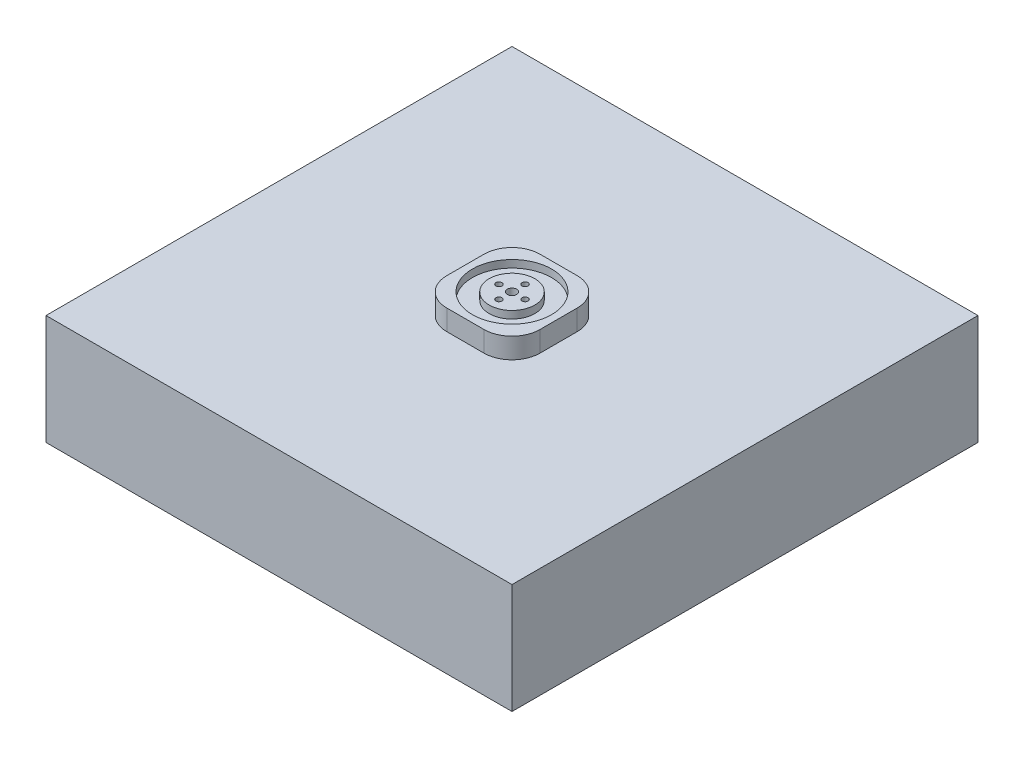
SolidWorks part; units mm, degrees
ref_plane "Front Plane" through (0, 0, 0) normal (0, 0, 1) x (1, 0, 0)
ref_plane "Top Plane" through (0, 0, 0) normal (0, 1, 0) x (1, 0, 0)
ref_plane "Right Plane" through (0, 0, 0) normal (1, 0, 0) x (0, 0, -1)
sketch "Sketch1" plane through (0, 0, 0) normal (0, 0, 1) x (1, 0, 0)
  line L0 (-22.5, 0) -> (22.5, 0)
  line L1 (-18, 9) -> (18, 9)
  line L2 (-18, 9) -> (-22.5, 0)
  line L3 (18, 9) -> (22.5, 0)
  point P4 (0, 0)
  point P8 (0, 9)
  dimension "D1" = 45
  dimension "D2" = 36
  dimension "D3" = 9
extrude "Boss-Extrude1" add sketch "Sketch1" along normal blind 44
sketch "Sketch3" plane through (0, 9, 0) normal (0, 1, 0) x (1, 0, 0)
  line L0 (18, -44) -> (18, 0) construction
  line L1 (-25, -47) -> (25, -47)
  line L2 (-25, -47) -> (-25, 3)
  line L3 (-25, 3) -> (25, 3)
  line L4 (25, -47) -> (25, 3)
  line L5 (-25, -47) -> (25, 3) construction
  line L6 (-25, 3) -> (25, -47) construction
  point P0 (0, -22)
  point P10 (18, -22)
  dimension "D1" = 50
  dimension "D2" = 50
extrude "Boss-Extrude2" add sketch "Sketch3" along normal blind 11
sketch "Sketch4" plane through (0, 20, 0) normal (0, 1, 0) x (1, 0, 0)
  line L0 (25, -47) -> (25, 3) construction
  circle A0 centre (0, -22) radius 12.25
  circle A1 centre (0, -22) radius 21.25
  point P6 (25, -22)
  dimension "D1" = 24.5
  dimension "D2" = 42.5
extrude "Cut-Extrude1" cut sketch "Sketch4" against normal blind 4
sketch "Sketch5" plane through (0, 20, 0) normal (0, 1, 0) x (1, 0, 0)
  circle A0 centre (0, -22) radius 12.25
  circle A1 centre (0, -22) radius 12.25 construction
  circle A2 centre (0, -22) radius 10.05
  circle A3 centre (0, -15) radius 1.6
  circle A4 centre (7, -22) radius 1.6
  circle A5 centre (0, -22) radius 10.05
  circle A6 centre (0, -29) radius 1.6
  circle A7 centre (0, -22) radius 10.05
  circle A8 centre (-7, -22) radius 1.6
  circle A9 centre (0, -22) radius 10.05
  circle A10 centre (0, -22) radius 2.5
  point P19 (0, -22)
  dimension "D1" = 20.1
  dimension "D2" = 3.2
  dimension "D5" = 5
  dimension "D3" = 7
  dimension "D4" = 4
extrude "Cut-Extrude3" cut sketch "Sketch5<3>" along direction (0, 1, 0) on the side against the normal up to surface (20 mm away) contours A3 | A8 | A4 | A6 region at (0, 20, 15) region at (7, 20, 22) region at (0, 20, 29) region at (-7, 20, 22) up to face at (0, 0, 22)
sketch "Sketch5<3>" plane through (0, 20, 0) normal (0, 1, 0) x (1, 0, 0) same geometry as "Sketch5"
extrude "Cut-Extrude4" cut sketch "Sketch5" against normal blind 5 contours A10 region at (0, 20, 22)
sketch "Sketch8" plane through (0, 0, 0) normal (0, -1, 0) x (-1, 0, 0)
  circle A0 centre (0, -29) radius 3
  circle A1 centre (-7, -22) radius 3
  circle A2 centre (0, -15) radius 3
  circle A3 centre (7, -22) radius 3
  dimension "D1" = 6
fillet "Fillet2" radius 15 4 edges at (-25, 14.5, 47) (-25, 14.5, -3) (25, 14.5, -3) (25, 14.5, 47)
sketch "Sketch9" plane through (0, 20, 0) normal (0, 1, 0) x (1, 0, 0)
  circle A0 centre (0, -22) radius 10
split line "Split Line1" [suppressed]
extrude "Cut-Extrude5" cut sketch "Sketch8" against normal offset from surface (15 mm away) 1 up to face at (-12.25, 16, 22)
sketch "Schizzo2" plane through (0, 0, 0) normal (0, -1, 0) x (1, 0, 0)
  line L0 (-22.5, 44) -> (-22.5, 0) construction
  line L1 (-125, 147) -> (125, 147)
  line L2 (-125, 147) -> (-125, -103)
  line L3 (-125, -103) -> (125, -103)
  line L4 (125, 147) -> (125, -103)
  line L5 (18, 44) -> (-18, 44) construction
  line L10 (-12.9476, 34.9476) -> (-12.9476, 8.2237)
  line L11 (-12.9476, 8.2237) -> (12.3261, 8.2237)
  line L12 (12.3261, 8.2237) -> (12.3261, 34.9476)
  line L13 (12.3261, 34.9476) -> (-12.9476, 34.9476)
  point P6 (-22.5, 22)
  point P7 (-125, 22)
  point P10 (0, 44)
  point P11 (0, 147)
  dimension "D1" = 250
  dimension "D2" = 250
extrude "Estrusione-Estrusione1" add sketch "Schizzo2" against normal up to surface (9 mm away) up to face at (0, 9, 22)
ref_plane "Piano1" through (0, 0, 0) normal (1, 0, 0) x (0, 0, -1)
ref_plane "Piano2" through (0, 0, 22) normal (0, 0, 1) x (1, 0, 0)
sketch "Schizzo5" plane through (0, 0, 0) normal (0, -1, 0) x (1, 0, 0)
  line L1 (-125, 147) -> (125, 147)
  line L2 (-125, 147) -> (-125, -103)
  line L3 (-125, -103) -> (125, -103)
  line L4 (125, 147) -> (125, -103)
  line L5 (-60.855, 82.8559) -> (60.855, 82.8559)
  line L6 (-60.855, 82.8559) -> (-60.855, -38.8559)
  line L7 (-60.855, -38.8559) -> (60.855, -38.8559)
  line L8 (60.855, 82.8559) -> (60.855, -38.8559)
  point P10 (-60.855, 22)
  point P13 (0, -38.8559)
  dimension "D1" = 121.7118
  dimension "D2" = 121.71
  dimension "D3" = 125
  dimension "D4" = 125
extrude "Estrusione-Estrusione2" add sketch "Schizzo5" along normal blind 50
